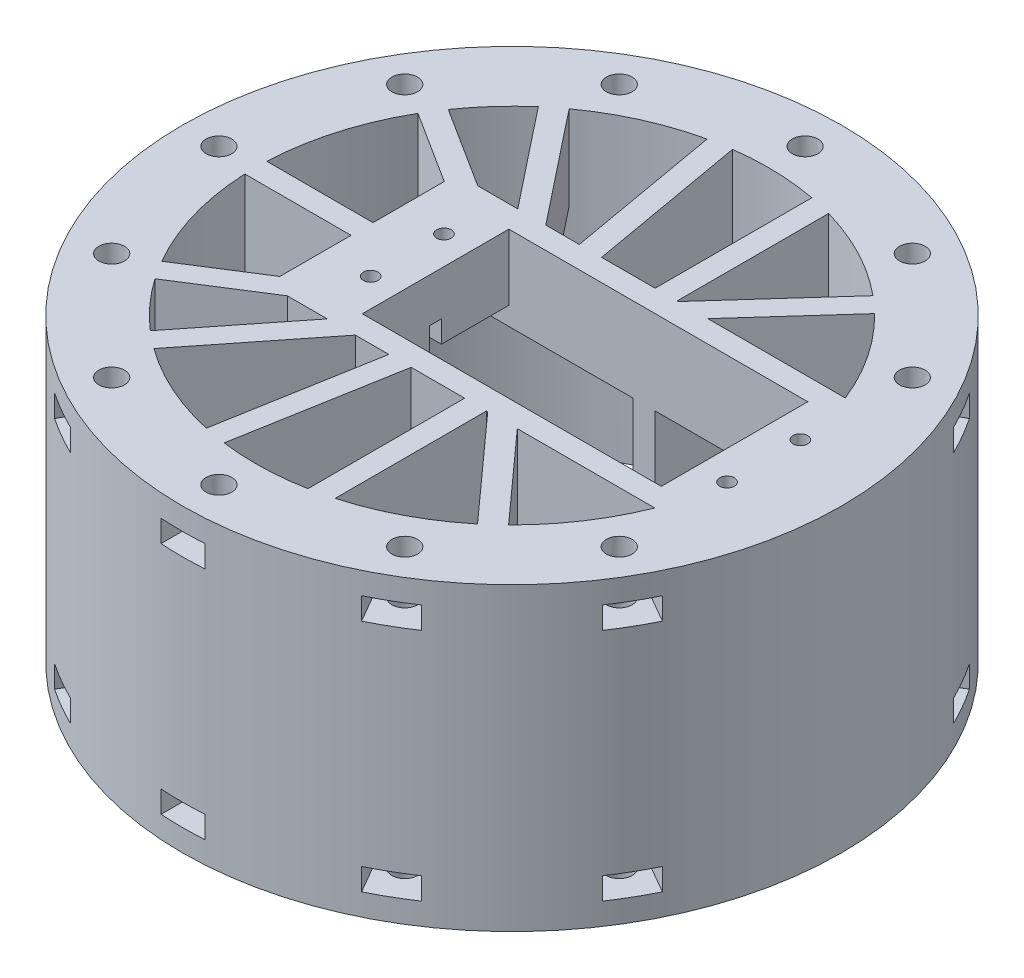
SolidWorks part; units mm, degrees
ref_plane "Front Plane" through (0, 0, 0) normal (0, 0, 1) x (1, 0, 0)
ref_plane "Top Plane" through (0, 0, 0) normal (0, 1, 0) x (1, 0, 0)
ref_plane "Right Plane" through (0, 0, 0) normal (1, 0, 0) x (0, 0, -1)
sketch "Sketch1" plane through (0, 0, 0) normal (0, 1, 0) x (1, 0, 0)
  line L0 (-43.0464, 0) -> (41.9462, 0) construction
  line L1 (0, 43.1152) -> (0, -41.8775) construction
  circle A1 centre (0, 0) radius 45
  dimension "D2" = 90
extrude "Boss-Extrude1" add sketch "Sketch1" along normal blind 41
sketch "Sketch2" plane through (0, 0, 0) normal (0, -1, 0) x (1, 0, 0)
  circle A0 centre (0, 0) radius 35
  dimension "D1" = 70
extrude "Cut-Extrude1" cut sketch "Sketch2" against normal blind 29.5
sketch "Sketch3" plane through (0, 29.5, 0) normal (0, -1, 0) x (1, 0, 0)
  line L0 (35, 0) -> (-35, 0) construction
  line L1 (0, -35) -> (0, 35) construction
  line L3 (37.5324, -10) -> (-17.4676, -10)
  line L4 (37.5324, -10) -> (37.5324, 10)
  line L5 (37.5324, 10) -> (-17.4676, 10)
  line L6 (-17.4676, -10) -> (-17.4676, 10)
  circle A0 centre (0, 0) radius 35 construction
  circle A1 centre (0, 0) radius 35 construction
  dimension "D1" = 20
  dimension "D2" = 55
  dimension "D3" = 10
  dimension "D4" = 37.5324
extrude "Cut-Extrude2" cut sketch "Sketch3" against normal blind 2.5 and the other way up to next
sketch "Sketch4" plane through (0, 32, 0) normal (0, -1, 0) x (1, 0, 0)
  line L0 (37.5324, 0) -> (-17.4676, 0) construction
  line L1 (37.5324, 10) -> (37.5324, -10) construction
  line L2 (-17.4676, 10) -> (-17.4676, -10) construction
  line L3 (0, -10) -> (0, 10) construction
  line L4 (-17.4676, -10) -> (33.541, -10) construction
  line L5 (33.541, 10) -> (-17.4676, 10) construction
  line L7 (30.3722, -10) -> (-10.4278, -10)
  line L8 (30.3722, -10) -> (30.3722, 10)
  line L9 (30.3722, 10) -> (-10.4278, 10)
  line L10 (-10.4278, -10) -> (-10.4278, 10)
  dimension "D1" = 20
  dimension "D2" = 40.8
  dimension "D3" = 30.3722
  dimension "D4" = 10
extrude "Cut-Extrude3" cut sketch "Sketch4" against normal blind 9
sketch "Sketch8" plane through (0, 29.5, 0) normal (0, -1, 0) x (1, 0, 0)
  line L0 (-17.4676, 0) -> (-35, 0) construction
  line L1 (-17.4676, 10) -> (-17.4676, -10) construction
  line L2 (8.0367, 10) -> (8.0367, 34.0648) construction
  line L3 (33.541, 10) -> (-17.4676, 10) construction
  line L4 (8.0367, -10) -> (8.0367, -29.3194) construction
  line L5 (-17.4676, -10) -> (33.541, -10) construction
  line L6 (6.5367, 10) -> (6.5367, 34.3842)
  line L7 (9.5367, 10) -> (9.5367, 33.6757)
  line L8 (9.5367, 10) -> (6.5367, 10)
  line L9 (9.5367, -10) -> (6.5367, -10)
  line L10 (6.5367, -10) -> (6.5367, -34.3842)
  line L11 (9.5367, -10) -> (9.5367, -33.6757)
  line L12 (-17.4676, 1.5) -> (-34.9678, 1.5)
  line L13 (-17.4676, -1.5) -> (-34.9678, -1.5)
  line L14 (-17.4676, 1.5) -> (-17.4676, -1.5)
  arc A0 (33.541, 10) -> (33.541, -10) centre (0, 0) ccw construction
  arc A1 (9.5367, 33.6757) -> (6.5367, 34.3842) centre (7.9531, 33.6757) ccw
  arc A2 (9.5367, -33.6757) -> (6.5367, -34.3842) centre (7.9531, -33.6757) cw
  arc A3 (-34.9678, 1.5) -> (-34.9678, -1.5) centre (-34.9678, 0) ccw
  dimension "D3" = 1.5
  dimension "D1" = 1.5
  dimension "D2" = 1.5
  dimension "D4" = 1.5
extrude "Boss-Extrude2" add sketch "Sketch8" along normal through all
sketch "Sketch16" plane through (0, 32, 0) normal (0, -1, 0) x (1, 0, 0)
  line L0 (-17.4676, 0) -> (37.5324, 0) construction
  line L1 (-17.4676, 10) -> (-17.4676, -10) construction
  line L2 (37.5324, -10) -> (37.5324, 10) construction
  line L3 (30.3722, -0.8) -> (37.5324, -0.8)
  line L4 (-10.4278, -0.8) -> (-17.4676, -0.8)
  line L5 (-10.4278, 10) -> (-10.4278, -10) construction
  line L6 (-10.4278, 0.8) -> (-17.4676, 0.8)
  line L7 (-17.4676, 0.8) -> (-17.4676, -0.8)
  line L8 (-10.4278, 0.8) -> (-10.4278, -0.8)
  line L9 (30.3722, -10) -> (30.3722, 10) construction
  line L10 (30.3722, 0.8) -> (37.5324, 0.8)
  line L11 (37.5324, 0.8) -> (37.5324, -0.8)
  line L12 (30.3722, 0.8) -> (30.3722, -0.8)
  dimension "D1" = 0.8
extrude "Cut-Extrude10" cut sketch "Sketch16" against normal blind 3
sketch "Sketch27" plane through (0, 0, 0) normal (0, -1, 0) x (1, 0, 0)
  line L0 (0, 0) -> (0, -53.17) construction
  line L1 (0, 0) -> (47.7582, -27.5732) construction
  line L3 (31.641, -18.2679) -> (31.641, -21.7321) construction
  line L4 (31.641, -21.7321) -> (34.641, -23.4641) construction
  line L5 (34.641, -23.4641) -> (37.641, -21.7321) construction
  line L6 (37.641, -21.7321) -> (37.641, -18.2679) construction
  line L7 (37.641, -18.2679) -> (34.641, -16.5359) construction
  line L8 (34.641, -16.5359) -> (31.641, -18.2679) construction
  circle A0 centre (0, 0) radius 40 construction
  circle A1 centre (34.641, -20) radius 1.75
  circle A2 centre (0, 0) radius 35 construction
  circle A3 centre (34.641, -20) radius 3 construction
  circle A4 centre (20, -34.641) radius 1.75
  circle A5 centre (0, -40) radius 1.75
  circle A6 centre (-20, -34.641) radius 1.75
  circle A7 centre (-34.641, -20) radius 1.75
  circle A8 centre (-40, 0) radius 1.75
  circle A9 centre (-34.641, 20) radius 1.75
  circle A10 centre (-20, 34.641) radius 1.75
  circle A11 centre (0, 40) radius 1.75
  circle A12 centre (20, 34.641) radius 1.75
  circle A13 centre (34.641, 20) radius 1.75
  circle A15 centre (40, 0) radius 1.75 [skipped]
  point P28 (0, 0)
  point P41 (0, 0)
  dimension "D1" = 80
  dimension "D3" = 3.5
  dimension "D4" = 70
  dimension "D5" = 6
  dimension "D6" = 12
  dimension "D2" = 60
extrude "Cut-Extrude15" cut sketch "Sketch27" against normal through all
ref_plane "Plane1" through (0, 38, 0) normal (0, 1, 0) x (1, 0, 0)
sketch "Sketch28" plane through (0, 38, 0) normal (0, 1, 0) x (1, 0, 0)
  line L0 (0, 0) -> (-54.493, 0) construction
  line L1 (-31.641, 18.2679) -> (-31.641, 21.7321)
  line L2 (-36.5359, 0) -> (-38.2679, 3)
  line L3 (-38.2679, 3) -> (-44.8999, 3)
  line L4 (-31.641, 21.7321) -> (-37.3844, 25.048)
  line L5 (-40.3844, 19.8519) -> (-34.641, 16.5359)
  line L6 (-44.8999, -3) -> (-38.2679, -3)
  line L7 (-38.2679, -3) -> (-36.5359, 0)
  line L8 (-43.4641, 0) -> (-42.5981, -1.5) [skipped]
  line L9 (-41.7321, 3) -> (-42.5981, 1.5) [skipped]
  line L10 (-34.641, 16.5359) -> (-31.641, 18.2679)
  line L11 (-18.2679, 31.641) -> (-16.5359, 34.641)
  line L12 (-16.5359, 34.641) -> (-19.8519, 40.3844)
  line L13 (-25.048, 37.3844) -> (-21.7321, 31.641)
  line L14 (-21.7321, 31.641) -> (-18.2679, 31.641)
  line L15 (0, 36.5359) -> (3, 38.2679)
  line L16 (3, 38.2679) -> (3, 44.8999)
  line L17 (-3, 44.8999) -> (-3, 38.2679)
  line L18 (-3, 38.2679) -> (0, 36.5359)
  line L19 (18.2679, 31.641) -> (21.7321, 31.641)
  line L20 (21.7321, 31.641) -> (25.048, 37.3844)
  line L21 (19.8519, 40.3844) -> (16.5359, 34.641)
  line L22 (16.5359, 34.641) -> (18.2679, 31.641)
  line L23 (31.641, 18.2679) -> (34.641, 16.5359)
  line L24 (34.641, 16.5359) -> (40.3844, 19.8519)
  line L25 (37.3844, 25.048) -> (31.641, 21.7321)
  line L26 (31.641, 21.7321) -> (31.641, 18.2679)
  line L31 (31.641, -18.2679) -> (31.641, -21.7321)
  line L32 (31.641, -21.7321) -> (37.3844, -25.048)
  line L33 (40.3844, -19.8519) -> (34.641, -16.5359)
  line L34 (34.641, -16.5359) -> (31.641, -18.2679)
  line L35 (18.2679, -31.641) -> (16.5359, -34.641)
  line L36 (16.5359, -34.641) -> (19.8519, -40.3844)
  line L37 (25.048, -37.3844) -> (21.7321, -31.641)
  line L38 (21.7321, -31.641) -> (18.2679, -31.641)
  line L39 (0, -36.5359) -> (-3, -38.2679)
  line L40 (-3, -38.2679) -> (-3, -44.8999)
  line L41 (3, -44.8999) -> (3, -38.2679)
  line L42 (3, -38.2679) -> (0, -36.5359)
  line L43 (-18.2679, -31.641) -> (-21.7321, -31.641)
  line L44 (-21.7321, -31.641) -> (-25.048, -37.3844)
  line L45 (-19.8519, -40.3844) -> (-16.5359, -34.641)
  line L46 (-16.5359, -34.641) -> (-18.2679, -31.641)
  line L47 (-31.641, -18.2679) -> (-34.641, -16.5359)
  line L48 (-34.641, -16.5359) -> (-40.3844, -19.8519)
  line L49 (-37.3844, -25.048) -> (-31.641, -21.7321)
  line L50 (-31.641, -21.7321) -> (-31.641, -18.2679)
  line L51 (36.5359, 0) -> (38.2679, -3) [skipped]
  line L52 (38.2679, -3) -> (44.8999, -3) [skipped]
  line L53 (44.8999, 3) -> (38.2679, 3) [skipped]
  line L54 (38.2679, 3) -> (36.5359, 0) [skipped]
  arc A0 (-44.8999, 3) -> (-44.8999, -3) centre (0, 0) ccw
  circle A1 centre (-40, 0) radius 3 construction
  arc A2 (-37.3844, 25.048) -> (-40.3844, 19.8519) centre (0, 0) ccw
  circle A3 centre (-34.641, 20) radius 3 construction
  arc A4 (-19.8519, 40.3844) -> (-25.048, 37.3844) centre (0, 0) ccw
  circle A5 centre (-20, 34.641) radius 3 construction
  arc A6 (3, 44.8999) -> (-3, 44.8999) centre (0, 0) ccw
  circle A7 centre (0, 40) radius 3 construction
  arc A8 (25.048, 37.3844) -> (19.8519, 40.3844) centre (0, 0) ccw
  circle A9 centre (20, 34.641) radius 3 construction
  arc A10 (40.3844, 19.8519) -> (37.3844, 25.048) centre (0, 0) ccw
  circle A11 centre (34.641, 20) radius 3 construction
  arc A14 (37.3844, -25.048) -> (40.3844, -19.8519) centre (0, 0) ccw
  circle A15 centre (34.641, -20) radius 3 construction
  arc A16 (19.8519, -40.3844) -> (25.048, -37.3844) centre (0, 0) ccw
  circle A17 centre (20, -34.641) radius 3 construction
  arc A18 (-3, -44.8999) -> (3, -44.8999) centre (0, 0) ccw
  circle A19 centre (0, -40) radius 3 construction
  arc A20 (-25.048, -37.3844) -> (-19.8519, -40.3844) centre (0, 0) ccw
  circle A21 centre (-20, -34.641) radius 3 construction
  arc A22 (-40.3844, -19.8519) -> (-37.3844, -25.048) centre (0, 0) ccw
  circle A23 centre (-34.641, -20) radius 3 construction
  arc A24 (44.8999, -3) -> (44.8999, 3) centre (0, 0) ccw [skipped]
  circle A25 centre (40, 0) radius 3 construction
  point P94 (0, 0)
  dimension "D1" = 90
  dimension "D2" = 6
  dimension "D3" = 12
extrude "Cut-Extrude17" cut sketch "Sketch28" against normal blind 3
sketch "Sketch29" plane through (0, 29.5, 0) normal (0, -1, 0) x (1, 0, 0)
  line L0 (32.4962, -13) -> (13.7255, -13)
  line L1 (9.5367, -33.6757) -> (9.5367, -10) construction
  line L2 (9.5367, -13) -> (9.5367, -33.6757)
  line L3 (9.5367, -10) -> (33.541, -10) construction
  line L4 (6.5367, -13) -> (-0.7691, -13)
  line L5 (6.5367, -10) -> (6.5367, -34.3842) construction
  line L6 (-20.4676, -11.223) -> (-20.4676, -1.5)
  line L7 (-34.9678, -1.5) -> (-17.4676, -1.5) construction
  line L8 (-20.4676, -1.5) -> (-34.9678, -1.5)
  line L9 (-17.4676, -0.8) -> (-17.4676, -10) construction
  line L10 (32.4962, 13) -> (13.7255, 13)
  line L11 (9.5367, 10) -> (9.5367, 33.6757) construction
  line L12 (9.5367, 13) -> (9.5367, 33.6757)
  line L13 (-7.5493, 34.1761) -> (-3.8154, 13)
  line L14 (6.5367, 13) -> (-0.7691, 13)
  line L15 (6.5367, 34.3842) -> (6.5367, 10) construction
  line L16 (-20.4676, 11.223) -> (-20.4676, 1.5)
  line L17 (-17.4676, 1.5) -> (-34.9678, 1.5) construction
  line L18 (-20.4676, 1.5) -> (-34.9678, 1.5)
  line L19 (6.5367, 13) -> (6.5367, 34.3842)
  line L20 (6.5367, -34.3842) -> (6.5367, -13)
  line L21 (0, 0) -> (-21.7353, -27.4331) construction
  line L22 (-20.5397, -28.3394) -> (-8.3862, -13)
  line L23 (-22.8911, -26.4764) -> (-12.2137, -13)
  line L24 (0, 0) -> (-20.4676, -13) construction
  line L25 (-17.6698, -13) -> (-28.713, -20.0141)
  line L26 (-20.4676, -11.223) -> (-30.3215, -17.4817)
  line L27 (0, 0) -> (-35, 0) construction
  line L28 (-20.4676, 11.223) -> (-30.3215, 17.4817)
  line L29 (-17.6698, 13) -> (-28.713, 20.0141)
  line L30 (-22.8911, 26.4764) -> (-12.2137, 13)
  line L31 (-20.5397, 28.3394) -> (-8.3862, 13)
  line L32 (-12.2137, 13) -> (-17.6698, 13)
  line L33 (0, 0) -> (-6.0777, -34.4683) construction
  line L34 (-4.5949, -34.6971) -> (-0.7691, -13)
  line L35 (-7.5493, -34.1761) -> (-3.8154, -13)
  line L36 (-3.8154, -13) -> (-17.6698, -13)
  line L37 (-4.5949, 34.6971) -> (-0.7691, 13)
  line L38 (-3.8154, 13) -> (-8.3862, 13)
  line L39 (0, 0) -> (23.4214, -26.0084) construction
  line L40 (9.6883, -13) -> (22.2852, -26.9883)
  line L41 (13.7255, -13) -> (24.5145, -24.9808)
  line L42 (13.7255, 13) -> (24.5145, 24.9808)
  line L43 (9.6883, 13) -> (22.2852, 26.9883)
  line L44 (9.6883, -13) -> (9.5367, -13)
  line L45 (9.6883, 13) -> (9.5367, 13)
  arc A0 (9.5367, -33.6757) -> (22.2852, -26.9883) centre (0, 0) ccw
  arc A1 (6.5367, 34.3842) -> (-4.5949, 34.6971) centre (0, 0) ccw
  arc A2 (32.4962, 13) -> (24.5145, 24.9808) centre (0, 0) ccw
  arc A3 (-34.9678, -1.5) -> (-30.3215, -17.4817) centre (0, 0) ccw
  circle A4 centre (0, 0) radius 35 construction
  arc A5 (-7.5493, 34.1761) -> (-20.5397, 28.3394) centre (0, 0) ccw
  arc A6 (-4.5949, -34.6971) -> (6.5367, -34.3842) centre (0, 0) ccw
  arc A7 (-20.5397, -28.3394) -> (-7.5493, -34.1761) centre (0, 0) ccw
  arc A8 (-28.713, -20.0141) -> (-22.8911, -26.4764) centre (0, 0) ccw
  arc A9 (-30.3215, 17.4817) -> (-34.9678, 1.5) centre (0, 0) ccw
  arc A10 (-22.8911, 26.4764) -> (-28.713, 20.0141) centre (0, 0) ccw
  arc A11 (24.5145, -24.9808) -> (32.4962, -13) centre (0, 0) ccw
  arc A12 (22.2852, 26.9883) -> (9.5367, 33.6757) centre (0, 0) ccw
  point P11 (21.5389, -10)
  point P23 (-17.4676, -5.4)
  line M3 (-17.4676, -1.5) -> (-34.9678, -1.5)
  arc M4 (-34.9678, -1.5) -> (6.5367, -34.3842) centre (0, 0) ccw
  line M5 (6.5367, -34.3842) -> (6.5367, -10)
  dimension "D1" = 1.5
  dimension "D2" = 3
  dimension "D3" = 3
  dimension "D4" = 80
  dimension "D5" = 1.5
  dimension "D6" = 1.5
  dimension "D7" = 1.5
sketch "Sketch32" plane through (0, 32, 0) normal (0, -1, 0) x (1, 0, 0)
  line L0 (-17.4676, 0) -> (37.5324, 0) construction
  line L1 (-17.4676, -1.5) -> (-17.4676, 1.5) construction
  line L2 (37.5324, 10) -> (37.5324, -10) construction
  line L3 (10.0324, 0) -> (10.0324, -10) construction
  line L6 (9.5367, -10) -> (33.541, -10) construction
  circle A0 centre (-14.2876, -5) radius 1
  circle A1 centre (-14.2876, 5) radius 1
  circle A2 centre (34.3524, -5) radius 1
  circle A3 centre (34.3524, 5) radius 1
  dimension "D1" = 24.32
  dimension "D3" = 2
  dimension "D2" = 5
extrude "Cut-Extrude21" cut sketch "Sketch32" against normal through all
extrude "Cut-Extrude22" cut sketch "Sketch29" against normal blind 12 contours L28 A9 L18 L16 | L26 L6 M3 M4 | L23 L36 L25 M4 | L35 L36 L22 M4 | L34 L4 M4 M5 | L2 A0 L40 L44 | L41 A11 L0 | L10 A2 L42 | L43 A12 L12 L45 | L19 A1 L37 L14 | L13 A5 L31 L38 | L30 A10 L29 L32 region at (23.89, 29.5, -17.1237) region at (13.9029, 29.5, -24.813) region at (1.8383, 29.5, -24.6789) region at (-27.5459, 29.5, -7.8919) region at (-10.8152, 29.5, -24.1049) region at (-20.9968, 29.5, -18.9781) region at (23.89, 29.5, 17.1237) region at (13.9029, 29.5, 24.813) region at (-10.8152, 29.5, 24.1049) region at (1.8383, 29.5, 24.6789) region at (-27.5459, 29.5, 7.8919) region at (-20.9968, 29.5, 18.9781)
sketch "Sketch33" plane through (0, 0, 1.5) normal (0, 0, 1) x (1, 0, 0)
  line L0 (-17.4676, 14.75) -> (-34.9678, 0)
  line L1 (-17.4676, 0) -> (-17.4676, 29.5) construction
  line L2 (-34.9678, 0) -> (-17.4676, 0)
  line L3 (-17.4676, 0) -> (-34.9678, 0) construction
  line L4 (-17.4676, 0) -> (-17.4676, 14.75)
extrude "Cut-Extrude23" cut sketch "Sketch33" against normal up to next
ref_plane "Plane2" through (0, 3, 0) normal (0, -1, 0) x (-1, 0, 0)
sketch "Sketch34" plane through (0, 3, 0) normal (0, -1, 0) x (-1, 0, 0)
  line L0 (0, 0) -> (0, 45) construction
  line L1 (18.2679, 31.641) -> (21.7321, 31.641)
  line L2 (0, 36.5359) -> (3, 38.2679)
  line L3 (3, 38.2679) -> (3, 44.8999)
  line L4 (21.7321, 31.641) -> (25.048, 37.3844)
  line L5 (19.8519, 40.3844) -> (16.5359, 34.641)
  line L6 (-3, 44.8999) -> (-3, 38.2679)
  line L7 (-3, 38.2679) -> (0, 36.5359)
  line L8 (0, 43.4641) -> (-1.5, 42.5981) [skipped]
  line L9 (3, 41.7321) -> (1.5, 42.5981) [skipped]
  line L10 (16.5359, 34.641) -> (18.2679, 31.641)
  line L11 (31.641, 18.2679) -> (34.641, 16.5359)
  line L12 (34.641, 16.5359) -> (40.3844, 19.8519)
  line L13 (37.3844, 25.048) -> (31.641, 21.7321)
  line L14 (31.641, 21.7321) -> (31.641, 18.2679)
  line L15 (36.5359, 0) -> (38.2679, -3)
  line L16 (38.2679, -3) -> (44.8999, -3)
  line L17 (44.8999, 3) -> (38.2679, 3)
  line L18 (38.2679, 3) -> (36.5359, 0)
  line L19 (31.641, -18.2679) -> (31.641, -21.7321)
  line L20 (31.641, -21.7321) -> (37.3844, -25.048)
  line L21 (40.3844, -19.8519) -> (34.641, -16.5359)
  line L22 (34.641, -16.5359) -> (31.641, -18.2679)
  line L23 (18.2679, -31.641) -> (16.5359, -34.641)
  line L24 (16.5359, -34.641) -> (19.8519, -40.3844)
  line L25 (25.048, -37.3844) -> (21.7321, -31.641)
  line L26 (21.7321, -31.641) -> (18.2679, -31.641)
  line L27 (0, -36.5359) -> (-3, -38.2679)
  line L28 (-3, -38.2679) -> (-3, -44.8999)
  line L29 (3, -44.8999) -> (3, -38.2679)
  line L30 (3, -38.2679) -> (0, -36.5359)
  line L31 (-18.2679, -31.641) -> (-21.7321, -31.641)
  line L32 (-21.7321, -31.641) -> (-25.048, -37.3844)
  line L33 (-19.8519, -40.3844) -> (-16.5359, -34.641)
  line L34 (-16.5359, -34.641) -> (-18.2679, -31.641)
  line L35 (-31.641, -18.2679) -> (-34.641, -16.5359)
  line L36 (-34.641, -16.5359) -> (-40.3844, -19.8519)
  line L37 (-37.3844, -25.048) -> (-31.641, -21.7321)
  line L38 (-31.641, -21.7321) -> (-31.641, -18.2679)
  line L43 (-31.641, 18.2679) -> (-31.641, 21.7321)
  line L44 (-31.641, 21.7321) -> (-37.3844, 25.048)
  line L45 (-40.3844, 19.8519) -> (-34.641, 16.5359)
  line L46 (-34.641, 16.5359) -> (-31.641, 18.2679)
  line L47 (-18.2679, 31.641) -> (-16.5359, 34.641)
  line L48 (-16.5359, 34.641) -> (-19.8519, 40.3844)
  line L49 (-25.048, 37.3844) -> (-21.7321, 31.641)
  line L50 (-21.7321, 31.641) -> (-18.2679, 31.641)
  line L51 (-36.5359, 0) -> (-38.2679, 3) [skipped]
  line L52 (-38.2679, 3) -> (-44.8999, 3) [skipped]
  line L53 (-44.8999, -3) -> (-38.2679, -3) [skipped]
  line L54 (-38.2679, -3) -> (-36.5359, 0) [skipped]
  circle A0 centre (0, 0) radius 45 construction
  circle A1 centre (0, 40) radius 3 construction
  arc A2 (3, 44.8999) -> (-3, 44.8999) centre (0, 0) ccw
  arc A3 (25.048, 37.3844) -> (19.8519, 40.3844) centre (0, 0) ccw
  circle A4 centre (20, 34.641) radius 3 construction
  arc A5 (40.3844, 19.8519) -> (37.3844, 25.048) centre (0, 0) ccw
  circle A6 centre (34.641, 20) radius 3 construction
  arc A7 (44.8999, -3) -> (44.8999, 3) centre (0, 0) ccw
  circle A8 centre (40, 0) radius 3 construction
  arc A9 (37.3844, -25.048) -> (40.3844, -19.8519) centre (0, 0) ccw
  circle A10 centre (34.641, -20) radius 3 construction
  arc A11 (19.8519, -40.3844) -> (25.048, -37.3844) centre (0, 0) ccw
  circle A12 centre (20, -34.641) radius 3 construction
  arc A13 (-3, -44.8999) -> (3, -44.8999) centre (0, 0) ccw
  circle A14 centre (0, -40) radius 3 construction
  arc A15 (-25.048, -37.3844) -> (-19.8519, -40.3844) centre (0, 0) ccw
  circle A16 centre (-20, -34.641) radius 3 construction
  arc A17 (-40.3844, -19.8519) -> (-37.3844, -25.048) centre (0, 0) ccw
  circle A18 centre (-34.641, -20) radius 3 construction
  arc A21 (-37.3844, 25.048) -> (-40.3844, 19.8519) centre (0, 0) ccw
  circle A22 centre (-34.641, 20) radius 3 construction
  arc A23 (-19.8519, 40.3844) -> (-25.048, 37.3844) centre (0, 0) ccw
  circle A24 centre (-20, 34.641) radius 3 construction
  arc A25 (-44.8999, 3) -> (-44.8999, -3) centre (0, 0) ccw [skipped]
  circle A26 centre (-40, 0) radius 3 construction
  point P98 (0, 0)
  dimension "D1" = 6
  dimension "D2" = 90
  dimension "D3" = 12
extrude "Cut-Extrude24" cut sketch "Sketch34" against normal blind 3
